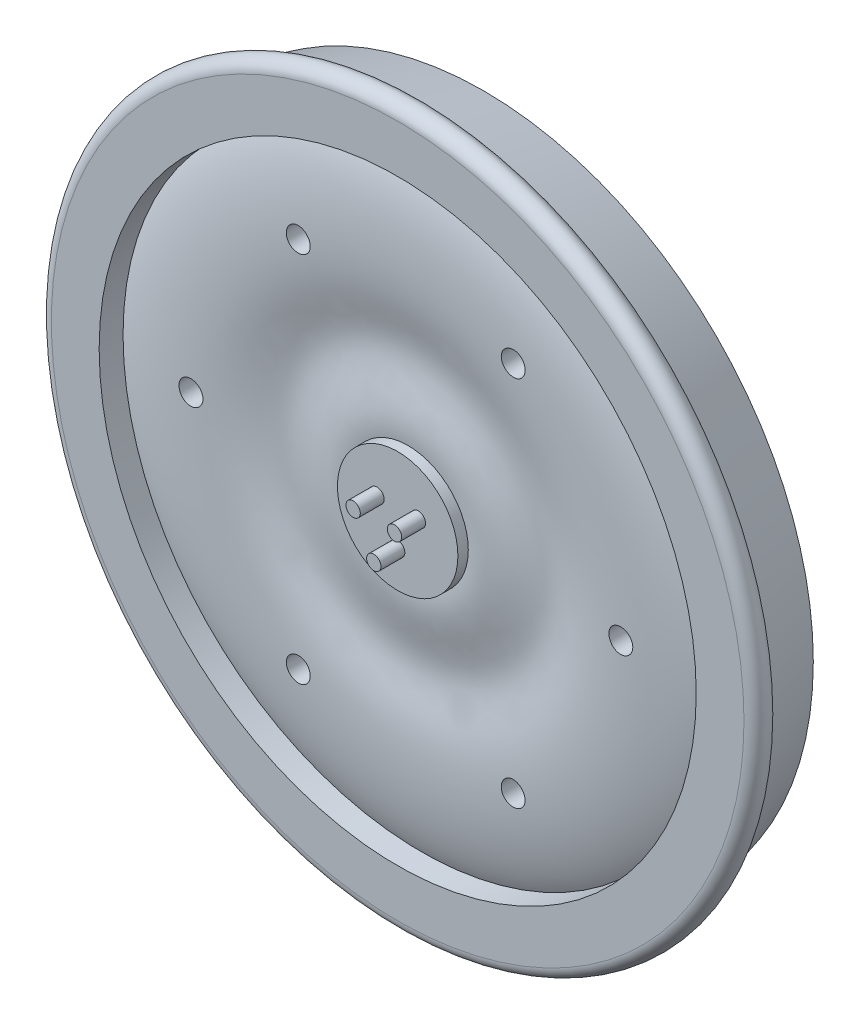
SolidWorks part; units mm, degrees
ref_plane "Front Plane" through (0, 0, 0) normal (0, 0, 1) x (1, 0, 0)
ref_plane "Top Plane" through (0, 0, 0) normal (0, 1, 0) x (1, 0, 0)
ref_plane "Right Plane" through (0, 0, 0) normal (1, 0, 0) x (0, 0, -1)
sketch "Sketch1" plane through (0, 0, 0) normal (0, 0, 1) x (1, 0, 0)
  circle A0 centre (0, 0) radius 750
  circle A1 centre (0, 0) radius 625
  dimension "D1" = 1500
  dimension "D2" = 1250
extrude "Boss-Extrude1" add sketch "Sketch1" along normal blind 50
fillet "Fillet1" 2 edges at (750, 0, 50) (750, 0, 0) type full round first side face at (750, 0, 50) second side face at (750, 0, 0) middle face at (750, 0, 50)
sketch "Sketch4" plane through (0, 0, 0) normal (1, 0, 0) x (0, 0, -1)
  line L0 (0, 0) -> (0, 725)
  line L1 (0, 725) -> (150, 684.8076) construction
  line L2 (150, 684.8076) -> (150, -0.9903) construction
  line L3 (130, 690.1666) -> (130, 540.1666)
  line L4 (122.256, 0) -> (0, 0)
  line L5 (130, 690.1666) -> (0, 725)
  line L6 (130, 540.1666) -> (100.0058, 540.1666)
  line L7 (122.256, 126.0832) -> (122.256, 0)
  arc A0 (122.256, 126.0832) -> (114.756, 133.5832) centre (114.756, 126.0832) ccw
  arc A1 (114.756, 133.5832) -> (105.6846, 140.6427) centre (113.054, 140.7542) cw
  spline S0 degree 3 poles (100.0058, 540.1666) (96.199, 512.6096) (86.0264, 445.2388) (114.2304, 352.8833) (111.021, 268.9405) (91.2518, 235.1191) (100.2737, 161.6867) (105.6846, 140.6427) knots 0.05115 0.05115 0.05115 0.05115 0.227447 0.329787 0.370281 0.63239 0.754578 0.754578 0.754578 0.754578
  dimension "D3" = 150
  dimension "D1" = 105
  dimension "D2" = 150
  dimension "D4" = 130
revolve "Revolve2" add sketch "Sketch4" angle 360 about L4
sketch "Sketch6" plane through (0, 0, 0) normal (0, 0, 1) x (1, 0, 0)
  circle A1 centre (0, 0) radius 126.0832
  circle A2 centre (0, 0) radius 126.0832
  dimension "D1" = 0
extrude "Boss-Extrude3" add sketch "Sketch6" along normal up to surface (50 mm away) up to face at (725, 0, 50)
sketch "Sketch7" plane through (0, 0, 0) normal (1, 0, 0) x (0, 0, -1)
  line L1 (-29.596, 0) -> (29.9071, 0)
  line L2 (29.9071, 0) -> (29.9071, 625)
  line L3 (29.9071, 625) -> (0, 625)
  spline S0 degree 3 poles (0, 625) (-31.984, 561.6656) (-43.8748, 379.644) (10.2338, 276.1436) (-54.8856, 132.6518) (1.6482, 44.9299) (-29.596, 0) knots 0 0 0 0 0.281537 0.495292 0.717767 1 1 1 1
revolve "Revolve3" add sketch "Sketch7" angle 360 about L1
sketch "Sketch8" plane through (0, 0, 50) normal (0, 0, 1) x (1, 0, 0)
  circle A0 centre (0, 0) radius 50 construction
  circle A1 centre (0, -50) radius 15
  dimension "D1" = 100
  dimension "D2" = 30
extrude "Boss-Extrude4" add sketch "Sketch8" along normal blind 50
pattern_circular "CirPattern1" count 3 over 360 about axis through (0, 0, 50) along (0, 0, 1) of "Boss-Extrude4"
sketch "Sketch9" plane through (0, 0, -122.256) normal (0, 0, -1) x (-1, 0, 0)
  line L1 (11.547, -103.9661) -> (5.7735, -93.9661)
  line L2 (5.7735, -93.9661) -> (-5.7735, -93.9661)
  line L3 (-5.7735, -93.9661) -> (-11.547, -103.9661)
  line L4 (-11.547, -103.9661) -> (-5.7735, -113.9661)
  line L5 (-5.7735, -113.9661) -> (5.7735, -113.9661)
  line L6 (5.7735, -113.9661) -> (11.547, -103.9661)
  line L7 (6.453, -101.9661) -> (-6.453, -101.9661)
  line L8 (6.453, -101.9661) -> (6.453, -105.9661)
  line L9 (6.453, -105.9661) -> (-6.453, -105.9661)
  line L10 (-6.453, -101.9661) -> (-6.453, -105.9661)
  circle A0 centre (0, -103.9661) radius 10 construction
  dimension "D5" = 20
  dimension "D1" = 8
  dimension "D2" = 8
  dimension "D3" = 18
  dimension "D4" = 18
extrude "Boss-Extrude5" add sketch "Sketch9" along normal blind 8
pattern_circular "CirPattern2" count 9 over 360 about axis through (0, 0, -122.256) along (0, 0, -1) of "Boss-Extrude5"
sketch "Sketch10" plane through (0, 0, -130) normal (0, 0, -1) x (-1, 0, 0)
  line L0 (0, -540.1666) -> (0, -690.1666) construction
  line L1 (34.641, -625.3248) -> (17.3205, -595.3248)
  line L2 (17.3205, -595.3248) -> (-17.3205, -595.3248)
  line L3 (-17.3205, -595.3248) -> (-34.641, -625.3248)
  line L4 (-34.641, -625.3248) -> (-17.3205, -655.3248)
  line L5 (-17.3205, -655.3248) -> (17.3205, -655.3248)
  line L6 (17.3205, -655.3248) -> (34.641, -625.3248)
  line L7 (-22.641, -617.3248) -> (22.641, -617.3248)
  line L8 (-22.641, -617.3248) -> (-22.641, -633.3248)
  line L9 (-22.641, -633.3248) -> (22.641, -633.3248)
  line L10 (22.641, -617.3248) -> (22.641, -633.3248)
  circle A0 centre (0, -625.3248) radius 30 construction
  circle A1 centre (0, 0) radius 540.1666 construction
  circle A2 centre (0, 0) radius 690.1666 construction
  dimension "D1" = 60
  dimension "D2" = 12
  dimension "D3" = 12
  dimension "D4" = 22
  dimension "D5" = 22
extrude "Boss-Extrude6" add sketch "Sketch10" along normal blind 10
pattern_circular "CirPattern3" count 6 over 360 about axis through (0, 0, -130) along (0, 0, -1) of "Boss-Extrude6"
sketch "Sketch11" plane through (0, 0, -130) normal (0, 0, -1) x (-1, 0, 0)
  line L0 (-875.7082, 0) -> (881.8752, 0) construction
  circle A0 centre (450, 0) radius 25
  circle A1 centre (-450, 0) radius 25
  dimension "D1" = 50
  dimension "D2" = 450
  dimension "D3" = 450
extrude "Cut-Extrude1" cut sketch "Sketch11" against normal up to next
pattern_circular "CirPattern4" count 3 over 360 about axis through (0, 0, -122.256) along (0, 0, -1) of "Cut-Extrude1"
